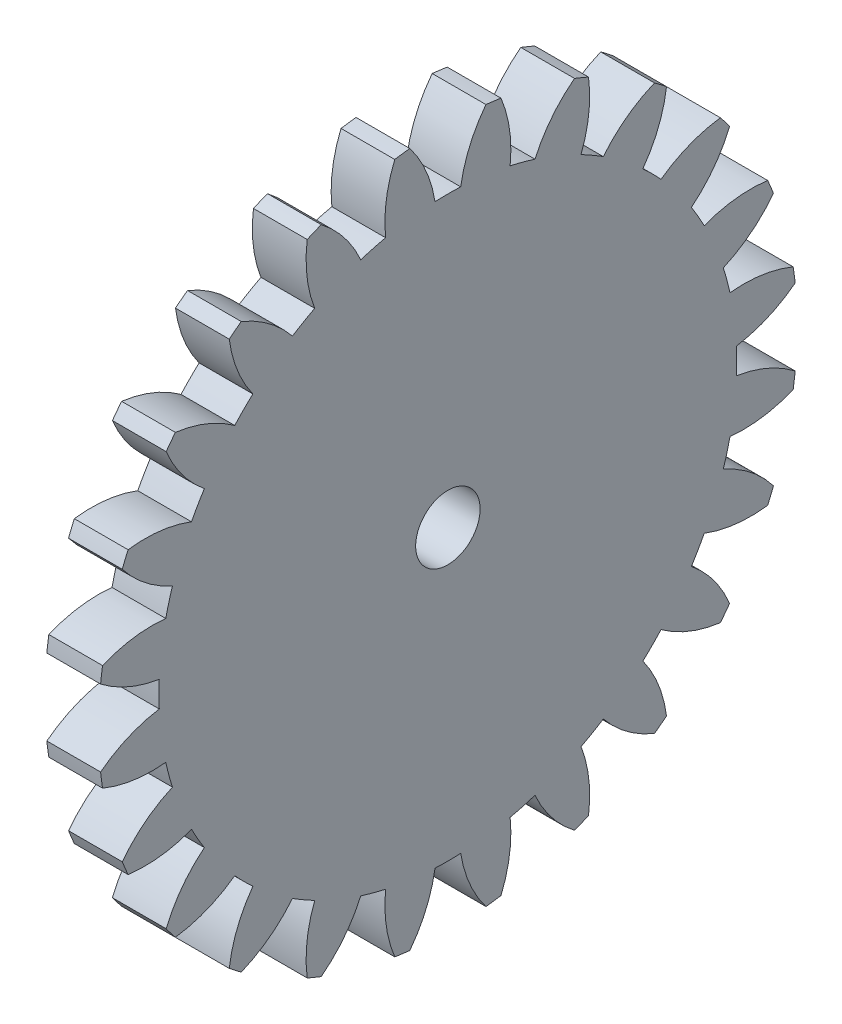
SolidWorks part; units mm, degrees
ref_plane "Plane1" through (0, 0, 0) normal (0, 0, 1) x (1, 0, 0)
ref_plane "Plane2" through (0, 0, 0) normal (0, 1, 0) x (1, 0, 0)
ref_plane "Plane3" through (0, 0, 0) normal (1, 0, 0) x (0, 0, -1)
sketch "HoldingSke" plane through (0, 0, 0) normal (0, 1, 0) x (1, 0, 0)
  line L0 (0, 0) -> (0.3654, -0.1627)
  line L1 (-15, 0) -> (100, 0) construction
  line L2 (0, 0) -> (-2.1039, 2.3779)
  line L3 (0, 0) -> (-11.863, 4.5341)
  line L4 (0, 0) -> (7.8894, 3.5126)
  line L5 (0, 0) -> (-46.8476, -17.4728)
  line L6 (0, 0) -> (-4.1448, -2.7965)
  line L7 (-2.1039, 2.3779) -> (8.6586, 51.2059)
  line L8 (-76.2, 54.61) -> (-75.2, 54.61)
  line L9 (-71.009, 38.7566) -> (-53.1078, 45.2721)
  line L10 (-76.2, 71.12) -> (104.1128, 71.12)
  line L11 (0, 0) -> (-5, 0)
  line L12 (-76.2, 101.6) -> (-76.113, 101.6)
  line L13 (24.9733, 27.94) -> (52.9518, 28.4284)
  line L14 (24.9733, 27.94) -> (24.9743, 27.94)
  line L15 (24.9733, 27.94) -> (100.4006, 29.5858)
  line L16 (-63.627, -2.5) -> (-12.827, -2.5)
  circle A0 centre (0, 0) radius 3
  circle A1 centre (0, 0) radius 26.874
  circle A2 centre (0, 0) radius 37.5
  circle A3 centre (0, 0) radius 3
  dimension "Pitch_radius" = 180.3128
sketch "BasProSke" plane through (0, 0, 0) normal (0, 1, 0) x (1, 0, 0)
  line L0 (-10, 0) -> (60, 0) construction
  line L1 (0, 0) -> (0, 32.5)
  line L2 (0, 0) -> (5, 0)
  line L3 (5, 0) -> (5, 32.5)
  line L4 (5, 32.5) -> (0, 32.5)
revolve "Base-Revolve" add sketch "BasProSke" angle 360 about L0
sketch "TooCutSke" plane through (0, 0, 0) normal (1, 0, 0) x (0, 0, -1)
  line L1 (0, 0) -> (0, 107) construction
  line L2 (0, 0) -> (-2.1143, 29.9254) construction
  line L3 (0, 0) -> (-7.8173, 59.3783) construction
  line L4 (-2.1143, 29.9254) -> (-3.9087, 29.6892) construction
  arc A0 (1.1963, 26.8474) -> (-1.1963, 26.8474) centre (0, 0) ccw
  arc A1 (3.5598, 32.33) -> (-3.5598, 32.33) centre (0, 0) ccw
  circle A2 centre (0, 0) radius 30 construction
  circle A3 centre (0, 0) radius 28.1908 construction
  arc A4 (-1.1963, 26.8474) -> (-3.5598, 32.33) centre (-13.0513, 24.9877) ccw
  arc A5 (3.5598, 32.33) -> (1.1963, 26.8474) centre (13.0513, 24.9877) ccw
extrude "ToothCut" cut sketch "TooCutSke" along normal through all
fillet "Breaks" [suppressed] radius 0.05 tangent propagation no
fillet "RootFillets" [suppressed] radius 0.626
pattern_circular "TeethCuts" count 24 every 15 about axis through (-10, 0, 0) along (1, 0, 0) of "ToothCut", "RootFillets", "Breaks"
sketch "HubNeaOneSke" plane through (0, 0, 0) normal (-1, 0, 0) x (0, 0, 1)
  circle A0 centre (0, 0) radius 26.874
extrude "HubNearOne" [suppressed] add sketch "HubNeaOneSke" along normal blind 45.0001
sketch "HubNeaBotSke" plane through (0, 0, 0) normal (-1, 0, 0) x (0, 0, 1)
  circle A0 centre (0, 0) radius 26.874
extrude "HubNearBoth" [suppressed] add sketch "HubNeaBotSke" along normal blind 22.5
ref_plane "FarPln" through (5, 0, 0) normal (1, 0, 0) x (0, 0, -1)
sketch "HubFarSke" plane through (5, 0, 0) normal (1, 0, 0) x (0, 0, -1)
  circle A0 centre (0, 0) radius 26.874
extrude "HubFar" [suppressed] add sketch "HubFarSke" along normal blind 22.5
sketch "BorSke" plane through (0, 0, 0) normal (1, 0, 0) x (0, 0, -1)
  circle A0 centre (0, 0) radius 3
  dimension "Diameter" = 6
extrude "Bore" cut sketch "BorSke" along normal mid plane 100.0001
sketch "KeySke" plane through (0, 0, 0) normal (1, 0, 0) x (0, 0, -1)
  line L0 (-1, 0) -> (-1, 4)
  line L1 (-1, 4) -> (1, 4)
  line L2 (1, 4) -> (1, 0)
  line L3 (0, 0) -> (0, 34) construction
  line L4 (-1, 0) -> (1, 0)
  dimension "Width" = 2
extrude "Keyway" [suppressed] cut sketch "KeySke" along normal mid plane 100.0001
pattern_circular "Keyway2" [suppressed] count 2 every 90 about axis through (-10, 0, 0) along (1, 0, 0) reverse direction yes
equation "' \"Module@HoldingSke\" = 6.35"
equation "' \"Num_teeth@HoldingSke\" = 12"
equation "' \"Ap@HoldingSke\" =  20"
equation "' \"Ap@HoldingSke\" = 20"
equation "' \"Width@HoldingSke\" = 0.5 * 25.4"
equation "' \"Hub_dia@HoldingSke\"= 1 * 25.4"
equation "' \"Hub_dia@HoldingSke\" = 1 * 25.4"
equation "' \"Overall_len@HoldingSke\" = 1.0 * 25.4"
equation "' \"Bore@HoldingSke\" = 0.75 * 25.4"
equation "' \"T_dim@HoldingSke\" = 0.1 * 25.4"
equation "' \"Width@KeySke\" = 0.25 * 25.4"
equation "' \"Show_teeth@HoldingSke\" = 13"
equation "' \"Backlash@HoldingSke\" = 0.009 * 25.4"
equation "' \"Addendum_fac@HoldingSke\" = 1.0"
equation "' \"Dedendum_fac@HoldingSke\" = 1.25"
equation "' \"Dedendum_add@HoldingSke\" = 0.00005 * 25.4"
equation "' \"Clearance_fac@HoldingSke\" = 0.25"
equation "\"Pitch@HoldingSke\" = 1 / \"Module@HoldingSke\""
equation "\"Overcut_dia@TooCutSke\" = (\"Num_teeth@HoldingSke\" + 2 * \"Addendum_fac@HoldingSke\") / \"Pitch@HoldingSke\" + 0.002 * 25.4"
equation "\"Pitch_dia@TooCutSke\" = \"Num_teeth@HoldingSke\" / \"Pitch@HoldingSke\""
equation "\"Base_dia@TooCutSke\" = \"Num_teeth@HoldingSke\" / \"Pitch@HoldingSke\" * cos((\"Ap@HoldingSke\"  * 3.14159265 / 180))"
equation "\"Root_dia@TooCutSke\" = (\"Num_teeth@HoldingSke\" + 2) / \"Pitch@HoldingSke\" - 2 * (\"Addendum_fac@HoldingSke\" + \"Dedendum_fac@HoldingSke\") / \"Pitch@HoldingSke\" - \"Dedendum_add@HoldingSke\" * 2"
equation "\"Half_ang@TooCutSke\" = 180 / \"Num_teeth@HoldingSke\""
equation "\"Half_CT@TooCutSke\" = \"Num_teeth@HoldingSke\" / \"Pitch@HoldingSke\" * sin((3.14159265 / 2 / \"Num_teeth@HoldingSke\")) / 2 - 7 * \"Backlash@HoldingSke\" / 4"
equation "\"Flank_rad@TooCutSke\" = \"Num_teeth@HoldingSke\" / \"Pitch@HoldingSke\" / 5"
equation "\"Radius@RootFillets\" = \"Clearance_fac@HoldingSke\" / \"Pitch@HoldingSke\" + \"Dedendum_add@HoldingSke\""
equation "\"Break_rad@Breaks\" = 0.02 / \"Pitch@HoldingSke\""
equation "\"Thickness@HoldingSke\" = \"Width@HoldingSke\""
equation "\"OAL@HoldingSke\" = \"Thickness@HoldingSke\""
equation "\"MHD@HoldingSke\" = (\"Num_teeth@HoldingSke\" + 2) / \"Pitch@HoldingSke\" - 2 * (\"Addendum_fac@HoldingSke\" + \"Dedendum_fac@HoldingSke\")  / \"Pitch@HoldingSke\" - \"Dedendum_add@HoldingSke\" * 2"
equation "\"MBD@HoldingSke\" = (\"Num_teeth@HoldingSke\" + 2) / \"Pitch@HoldingSke\" - 2 * (\"Addendum_fac@HoldingSke\" + \"Dedendum_fac@HoldingSke\")  / \"Pitch@HoldingSke\" - \"Dedendum_add@HoldingSke\" * 2 - 0.002 * 25.4"
equation "\"MHD@HoldingSke\" = ((sgn( \"MHD@HoldingSke\" - \"Hub_dia@HoldingSke\" )-1)*( \"MHD@HoldingSke\" - \"Hub_dia@HoldingSke\" ))/-2+ \"Hub_dia@HoldingSke\""
equation "\"MBD@HoldingSke\" = ((sgn( \"MBD@HoldingSke\" - \"Bore@HoldingSke\" )-1)*( \"MBD@HoldingSke\" - \"Bore@HoldingSke\" ))/-2+ \"Bore@HoldingSke\""
equation "\"OAL@HoldingSke\" = ((sgn( \"OAL@HoldingSke\" - \"Overall_len@HoldingSke\" )+1)*( \"OAL@HoldingSke\" - \"Overall_len@HoldingSke\" ))/2 + \"Overall_len@HoldingSke\" + 0.000002 * 25.4"
equation "\"Num_teeth@TeethCuts\" = int( \"Show_teeth@HoldingSke\" ) + 1"
equation "\"Num_teeth@TeethCuts\" = ((sgn( \"Num_teeth@TeethCuts\" - \"Num_teeth@HoldingSke\" )-1)*( \"Num_teeth@TeethCuts\" - \"Num_teeth@HoldingSke\" ))/-2+ \"Num_teeth@HoldingSke\""
equation "\"Num_teeth@TeethCuts\" = ((sgn( \"Num_teeth@TeethCuts\" - 2.0)+1)*( \"Num_teeth@TeethCuts\" - 2.0))/2 +2.0"
equation "\"Angle@TeethCuts\" = 360.0 / \"Num_teeth@HoldingSke\""
equation "\"Diameter@BasProSke\" = (\"Num_teeth@HoldingSke\" + 2 * \"Addendum_fac@HoldingSke\") / \"Pitch@HoldingSke\""
equation "\"Thickness@BasProSke\"  = \"Thickness@HoldingSke\""
equation "' \"Fillet_rad@BasProSke\" =  \"Thickness@HoldingSke\" * 0.05"
equation "' \"Fillet_rad@BasProSke\" = \"Thickness@HoldingSke\" * 0.05"
equation "\"MHD@HoldingSke\" = ((sgn( \"MHD@HoldingSke\" - \"Root_dia@TooCutSke\" )-1)*( \"MHD@HoldingSke\" - \"Root_dia@TooCutSke\" ))/-2+ \"Root_dia@TooCutSke\""
equation "\"Diameter@HubNeaOneSke\" = \"MHD@HoldingSke\""
equation "\"Length@HubNearOne\" = \"OAL@HoldingSke\" - \"Thickness@BasProSke\""
equation "\"Diameter@HubNeaBotSke\" = \"MHD@HoldingSke\""
equation "\"Length@HubNearBoth\" = ( \"OAL@HoldingSke\" - \"Thickness@BasProSke\" ) / 2.0"
equation "\"Thickness@FarPln\" = \"Thickness@BasProSke\""
equation "\"Diameter@HubFarSke\" = \"MHD@HoldingSke\""
equation "\"Length@HubFar\" = ( \"OAL@HoldingSke\" - \"Thickness@BasProSke\" ) / 2.0"
equation "\"Diameter@BorSke\" = \"MBD@HoldingSke\""
equation "\"D1@Bore\" = \"OAL@HoldingSke\" * 2.0"
equation "\"D1@Keyway\" = \"OAL@HoldingSke\" * 2.0"
equation "\"Offset@KeySke\" = \"T_dim@HoldingSke\" + \"MBD@HoldingSke\" / 2.0"
